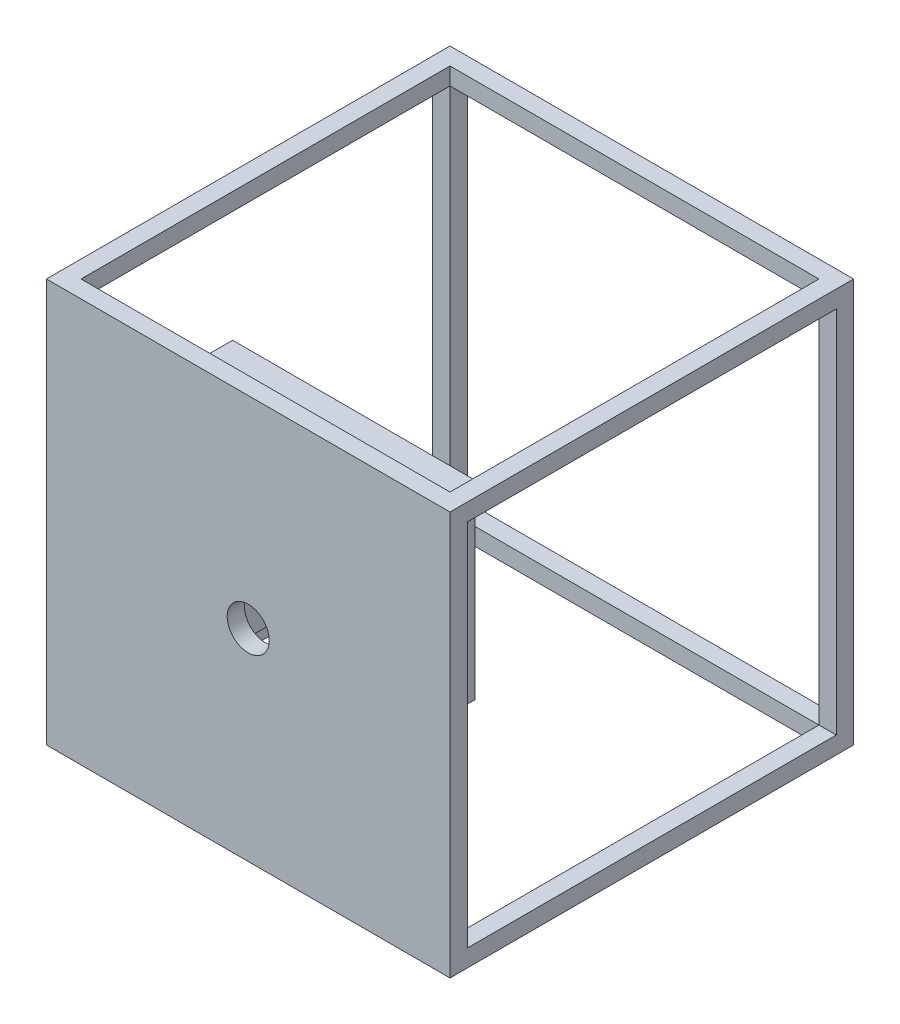
SolidWorks part; units mm, degrees
ref_plane "Piano frontale" through (0, 0, 0) normal (0, 0, 1) x (1, 0, 0)
ref_plane "Piano superiore" through (0, 0, 0) normal (0, 1, 0) x (1, 0, 0)
ref_plane "Piano destro" through (0, 0, 0) normal (1, 0, 0) x (0, 0, -1)
sketch "Schizzo1" plane through (0, 0, 0) normal (0, 0, 1) x (1, 0, 0)
  line L1 (-35, 35) -> (35, 35)
  line L2 (-35, 35) -> (-35, -35)
  line L3 (-35, -35) -> (35, -35)
  line L4 (35, 35) -> (35, -35)
  line L5 (-35, 35) -> (35, -35) construction
  line L6 (-35, -35) -> (35, 35) construction
  point P0 (0, 0)
  dimension "D2" = 70
extrude "Estrusione-Estrusione1" add sketch "Schizzo1" along normal blind 70
sketch "Schizzo3" plane through (0, 0, 0) normal (0, 0, -1) x (-1, 0, 0)
  line L0 (-35, -35) -> (-35, 35) construction
  line L1 (-32, 32) -> (32, 32)
  line L2 (-32, 32) -> (-32, -32)
  line L3 (-32, -32) -> (32, -32)
  line L4 (32, 32) -> (32, -32)
  line L5 (-32, 32) -> (32, -32) construction
  line L6 (-32, -32) -> (32, 32) construction
  point P0 (0, 0)
  dimension "D1" = 3
extrude "Taglio-Estrusione2" cut sketch "Schizzo3" against normal offset from surface (67 mm away) 3 up to face at (0, 0, 70)
sketch "Schizzo2" plane through (0, 0, 70) normal (0, 0, 1) x (1, 0, 0)
  circle A0 centre (0, 0) radius 3.65
  dimension "D1" = 7.3
extrude "Taglio-Estrusione1" cut sketch "Schizzo2" against normal up to next
sketch "Schizzo4" plane through (0, -35, 0) normal (0, -1, 0) x (1, 0, 0)
  line L0 (-35, 70) -> (-35, 0) construction
  line L1 (-32, 67) -> (32, 67)
  line L2 (-32, 67) -> (-32, 3)
  line L3 (-32, 3) -> (32, 3)
  line L4 (32, 67) -> (32, 3)
  line L5 (-32, 67) -> (32, 3) construction
  line L6 (-32, 3) -> (32, 67) construction
  line L7 (-35, 70) -> (35, 70) construction
  point P0 (0, 35)
  point P9 (0, 0)
  dimension "D1" = 3
  dimension "D2" = 3
extrude "Taglio-Estrusione3" cut sketch "Schizzo4" against normal up to next
ref_plane "Piano1" through (0, 0, 0) normal (-0.7071, 0.7071, 0) x (0, 0, 1)
mirror "Specchia1" about plane through (0, 0, 0) normal (-0.7071, 0.7071, 0) of "Taglio-Estrusione3"
mirror "Specchia2" about plane through (0, 0, 0) normal (-0.7071, 0.7071, 0) of "Specchia1"
sketch "Schizzo5" plane through (0, 0, 67) normal (0, 0, -1) x (-1, 0, 0)
  line L0 (0, 0) -> (0, 3.65) construction
  line L1 (-21, 23.65) -> (21, 23.65)
  line L3 (-8, 4.65) -> (8, 4.65)
  line L7 (-21, 23.65) -> (-21, -9.35)
  line L10 (-21, -9.35) -> (-8, -9.35)
  line L11 (-8, 4.65) -> (-8, -9.35)
  line L14 (21, -9.35) -> (8, -9.35)
  line L15 (8, 4.65) -> (8, -9.35)
  line L16 (21, 23.65) -> (21, -9.35)
  circle A3 centre (0, 0) radius 3.65 construction
  point P0 (0, 4.65)
  point P1 (0, 0)
  point P6 (0, 0)
  point P13 (0, 3.65)
  dimension "D3" = 1
  dimension "D1" = 13
  dimension "D2" = 42
  dimension "D4" = 14
  dimension "D5" = 33
extrude "Estrusione-Estrusione2" add sketch "Schizzo5" along normal blind 15.3
sketch "Schizzo6" plane through (0, 0, 51.7) normal (0, 0, -1) x (-1, 0, 0)
  line L0 (0, 39.2219) -> (0, -42.1384) construction
  circle A0 centre (-17.5, 7.5) radius 1.5
  circle A1 centre (17.5, 7.5) radius 1.5
  dimension "D1" = 7.5
  dimension "D3" = 3
  dimension "D2" = 17.5
extrude "Taglio-Estrusione4" cut sketch "Schizzo6" against normal blind 3
